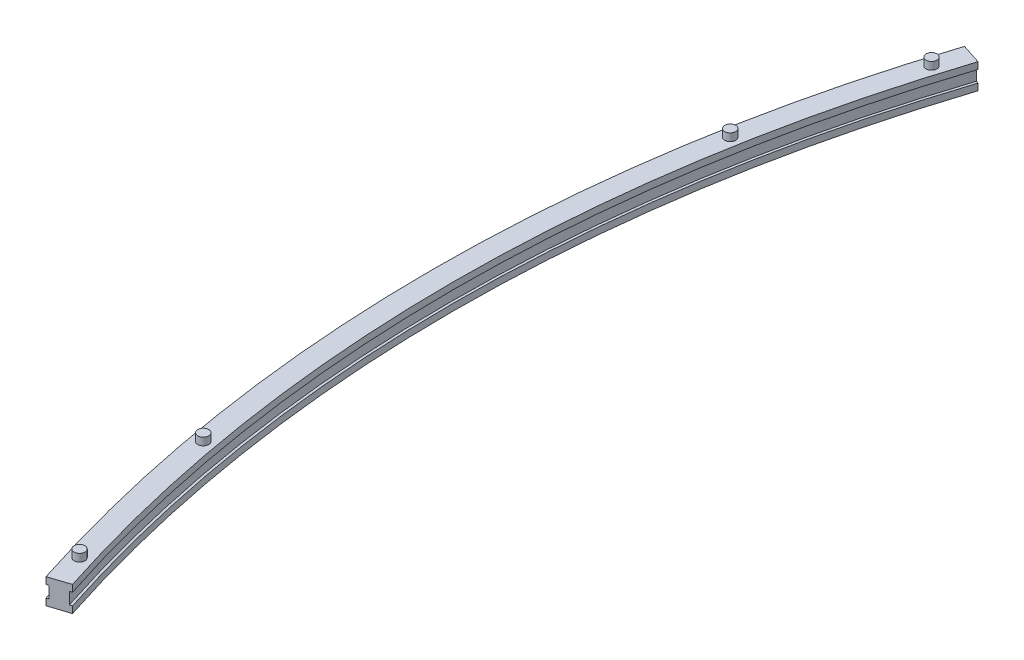
SolidWorks part; units mm, degrees
ref_plane "Front Plane" through (0, 0, 0) normal (0, 0, 1) x (1, 0, 0)
ref_plane "Top Plane" through (0, 0, 0) normal (0, 1, 0) x (1, 0, 0)
ref_plane "Right Plane" through (0, 0, 0) normal (1, 0, 0) x (0, 0, -1)
sketch "Sketch1" plane through (0, 0, 0) normal (0, 1, 0) x (1, 0, 0)
  line L0 (-167.932, 50.621) -> (-167.932, -50.621) construction
  line L1 (-172.538, 31.31) -> (-172.538, -31.31) construction
  line L2 (-173.7679, -31.5332) -> (-171.3081, -31.0868) construction
  line L3 (-169.0907, -50.9703) -> (-166.6971, -50.2487) construction
  line L4 (-165.5845, -53.8017) -> (-167.9622, -54.5742)
  line L5 (-165.5845, 53.8017) -> (-167.9622, 54.5742)
  arc A0 (-167.9622, 54.5742) -> (-167.9622, -54.5742) centre (0, 0) ccw
  arc A1 (-165.5845, 53.8017) -> (-165.5845, -53.8017) centre (0, 0) ccw
  circle A2 centre (-172.538, -31.31) radius 0.65
  circle A3 centre (-172.538, 31.31) radius 0.65
  circle A4 centre (-167.932, 50.621) radius 0.65
  circle A5 centre (-167.932, -50.621) radius 0.65
  point P0 (-167.932, 50.621)
  point P1 (-172.538, 31.31)
  point P4 (-167.932, -50.621)
  point P5 (-167.932, 0)
  point P6 (-172.538, -31.31)
  point P7 (-172.538, 0)
  point P24 (0, 0)
  dimension "D7" = 1.3
  dimension "D1" = 50.621
  dimension "D2" = 31.31
  dimension "D3" = 172.538
  dimension "D4" = 167.932
  dimension "D5" = 2.5
  dimension "D6" = 36
extrude "Boss-Extrude1" add sketch "Sketch1" along normal blind 0.8 contours A2 | A1 L5 A0 L4 A2 | A5 | A3 | A4 region at (-167.1123, 0, 53.1446) region at (-172.538, 0, 31.31) region at (-172.538, 0, -31.31) region at (-167.932, 0, -50.621) region at (-167.932, 0, 50.621)
sketch "Sketch2" plane through (0, 0.8, 0) normal (0, 1, 0) x (1, 0, 0)
  line L2 (-165.5845, 53.8017) -> (-167.9622, 54.5742)
  line L3 (-167.9622, -54.5742) -> (-165.5845, -53.8017)
  line L4 (-165.8698, 53.8944) -> (-167.6768, 54.4815)
  line L5 (-167.6768, -54.4815) -> (-165.8698, -53.8944)
  arc A0 (-167.6768, 54.4815) -> (-167.6768, -54.4815) centre (0, 0) ccw
  arc A1 (-165.8698, 53.8944) -> (-165.8698, -53.8944) centre (0, 0) ccw
  arc A2 (-165.5845, 53.8017) -> (-165.5845, -53.8017) centre (0, 0) ccw
  arc A3 (-167.9622, 54.5742) -> (-167.9622, -54.5742) centre (0, 0) ccw
  dimension "D1" = 0
extrude "Boss-Extrude2" add sketch "Sketch2" along normal blind 1.4
sketch "Sketch3" plane through (0, 2.2, 0) normal (0, 1, 0) x (1, 0, 0)
  line L2 (-167.9622, -54.5742) -> (-165.5845, -53.8017)
  line L3 (-165.5845, 53.8017) -> (-167.9622, 54.5742)
  line L4 (-167.9622, -54.5742) -> (-165.5845, -53.8017)
  line L5 (-165.5845, 53.8017) -> (-167.9622, 54.5742)
  arc A2 (-165.5845, 53.8017) -> (-165.5845, -53.8017) centre (0, 0) ccw
  arc A3 (-167.9622, 54.5742) -> (-167.9622, -54.5742) centre (0, 0) ccw
  arc A4 (-165.5845, 53.8017) -> (-165.5845, -53.8017) centre (0, 0) ccw
  arc A5 (-167.9622, 54.5742) -> (-167.9622, -54.5742) centre (0, 0) ccw
  dimension "D1" = 0
extrude "Boss-Extrude3" add sketch "Sketch3" along normal blind 0.8
extrude "Boss-Extrude4" add sketch "Sketch1<3>" along normal blind 3.9 contours A2 | A4 | A5 | A3 region at (-172.538, 0, 31.31) region at (-167.932, 0, -50.621)
sketch "Sketch1<3>" plane through (0, 0, 0) normal (0, 1, 0) x (1, 0, 0) same geometry as "Sketch1"
